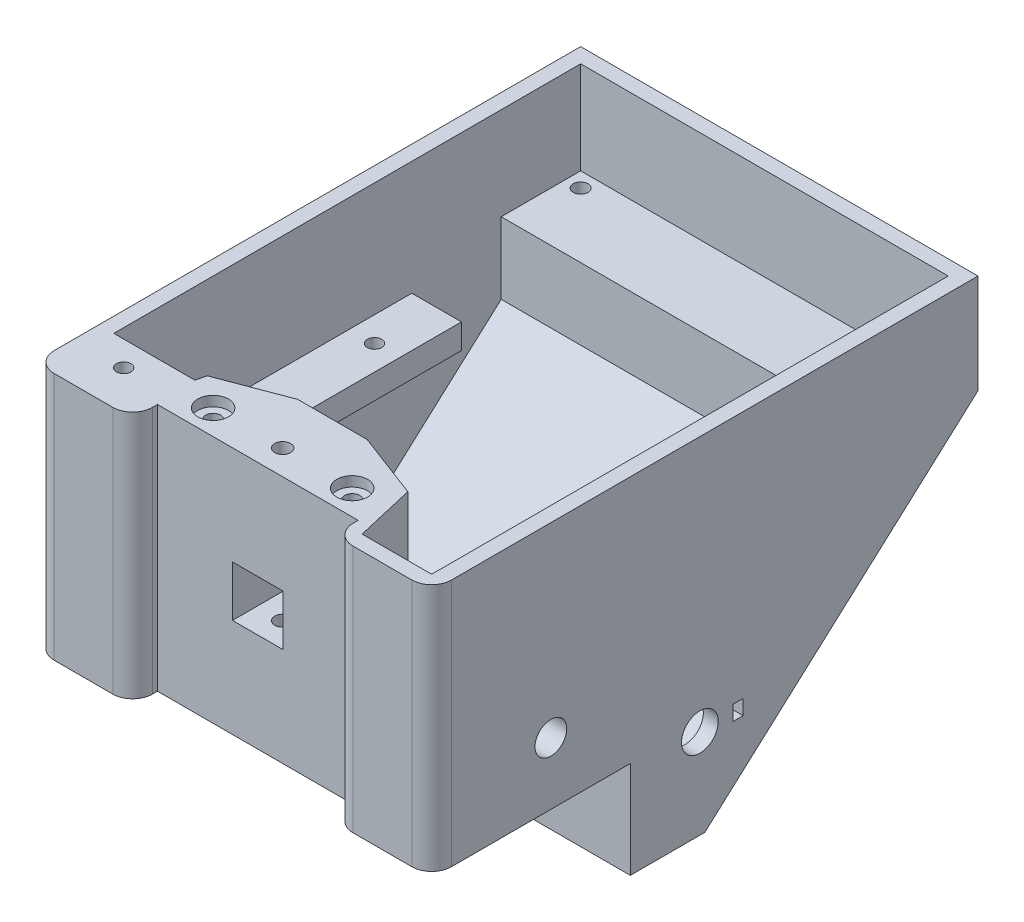
SolidWorks part; units mm, degrees
ref_plane "Спереди" through (0, 0, 0) normal (0, 0, 1) x (1, 0, 0)
ref_plane "Сверху" through (0, 0, 0) normal (0, 1, 0) x (1, 0, 0)
ref_plane "Справа" through (0, 0, 0) normal (1, 0, 0) x (0, 0, -1)
sketch "Sketch2" plane through (0, 0, 0) normal (1, 0, 0) x (0, 0, -1)
  line L0 (-27.3205, 20.9982) -> (-27.3205, -29.0018)
  line L1 (-27.3205, -29.0018) -> (12.6795, -29.0018)
  line L2 (12.6795, -29.0018) -> (12.6795, -48.5114)
  line L3 (12.6795, -48.5114) -> (27.6795, -48.5114)
  line L4 (82.6795, 20.9982) -> (82.6795, 0.9982)
  line L5 (82.6795, 20.9982) -> (-27.3205, 20.9982)
  line L6 (82.6795, 0.9982) -> (27.6795, -48.5114)
  dimension "D1" = 110
  dimension "D2" = 50
  dimension "D3" = 40
  dimension "D4" = 15
  dimension "D5" = 20
extrude "Boss-Extrude1" add sketch "Sketch2" along normal blind 80
shell "Shell1" thickness 3 removed face at (40, 20.9982, -27.6795)
sketch "Sketch3" plane through (0, 0, 24.3205) normal (0, 0, -1) x (-1, 0, 0)
  line L0 (-40, 20.9982) -> (-40, -26.0018) construction
  line L3 (-77, 20.9982) -> (-3, 20.9982) construction
  line L4 (-77, -26.0018) -> (-3, -26.0018) construction
  line L6 (-17, 20.9982) -> (-63, 20.9982)
  line L7 (-17, 20.9982) -> (-17, -26.0018)
  line L8 (-17, -26.0018) -> (-63, -26.0018)
  line L9 (-63, 20.9982) -> (-63, -26.0018)
  line L10 (-17, 20.9982) -> (-63, -26.0018) construction
  line L11 (-17, -26.0018) -> (-63, 20.9982) construction
  point P6 (-40, -2.5018)
  dimension "D1" = 46
extrude "Boss-Extrude2" add sketch "Sketch3" along normal blind 17
sketch "Sketch4" plane through (0, 0, 27.3205) normal (0, 0, 1) x (1, 0, 0)
  line L0 (0, 20.9982) -> (80, -29.0018) construction
  line L2 (45.1, -9.1018) -> (34.9, -9.1018)
  line L3 (45.1, -9.1018) -> (45.1, 1.0982)
  line L4 (45.1, 1.0982) -> (34.9, 1.0982)
  line L5 (34.9, -9.1018) -> (34.9, 1.0982)
  line L6 (45.1, -9.1018) -> (34.9, 1.0982) construction
  line L7 (45.1, 1.0982) -> (34.9, -9.1018) construction
  point P4 (40, -4.0018)
  dimension "D1" = 10.2
extrude "Cut-Extrude1" cut sketch "Sketch4" against normal up to surface (20 mm away) up to face at (40, -2.5018, 7.3205)
sketch "Sketch6" plane through (0, -29.0018, 0) normal (0, -1, 0) x (1, 0, 0)
  line L0 (40, 27.3205) -> (40, -12.6795) construction
  line L1 (47.5, -5.4795) -> (32.5, -5.4795)
  line L2 (47.5, -5.4795) -> (47.5, 7.3205)
  line L3 (47.5, 7.3205) -> (32.5, 7.3205)
  line L4 (32.5, -5.4795) -> (32.5, 7.3205)
  line L5 (47.5, -5.4795) -> (32.5, 7.3205) construction
  line L6 (47.5, 7.3205) -> (32.5, -5.4795) construction
  line L7 (80, -12.6795) -> (0, -12.6795) construction
  line L9 (80, 27.3205) -> (0, 27.3205) construction
  point P0 (40, 0.9205)
  dimension "D1" = 15
  dimension "D2" = 12.8
  dimension "D4" = 20
extrude "Cut-Extrude2" cut sketch "Sketch6" against normal up to surface (3 mm away) up to face at (40, -26.0018, 10.0705)
sketch "Sketch7" plane through (0, 0, 27.3205) normal (0, 0, 1) x (1, 0, 0)
  line L0 (40, 20.9982) -> (40, -29.0018) construction
  line L1 (80, 20.9982) -> (0, 20.9982) construction
  line L2 (80, -29.0018) -> (0, -29.0018) construction
  line L4 (60.2, -29.0018) -> (19.8, -29.0018)
  line L5 (60.2, -29.0018) -> (60.2, 20.9982)
  line L6 (60.2, 20.9982) -> (19.8, 20.9982)
  line L7 (19.8, -29.0018) -> (19.8, 20.9982)
  line L8 (60.2, -29.0018) -> (19.8, 20.9982) construction
  line L9 (60.2, 20.9982) -> (19.8, -29.0018) construction
  point P6 (40, -4.0018)
  dimension "D1" = 40.4
extrude "Cut-Extrude3" cut sketch "Sketch7" against normal blind 5
fillet "Fillet1" radius 4 4 edges at (19.8, -4.0018, 27.3205) (60.2, -4.0018, 27.3205) (80, -4.0018, 27.3205) (0, -4.0018, 27.3205)
sketch "Sketch12" plane through (0, 20.9982, 0) normal (0, 1, 0) x (1, 0, 0)
  line L0 (19.8, -22.3205) -> (19.8, -12.3205) construction
  line L1 (19.8, -12.3205) -> (60.2, -12.3205) construction
  line L2 (60.2, -12.3205) -> (60.2, -22.3205) construction
  line L3 (33, -7.3205) -> (19.8, -12.3205)
  line L4 (17, -7.3205) -> (63, -7.3205) construction
  line L5 (19.8, -12.3205) -> (17, -24.3205)
  line L6 (17, -24.3205) -> (17, -7.3205)
  line L7 (17, -7.3205) -> (33, -7.3205)
  line L8 (47, -7.3205) -> (63, -7.3205)
  line L9 (63, -7.3205) -> (63, -24.3205)
  line L10 (63, -24.3205) -> (60.2, -12.3205)
  line L11 (60.2, -12.3205) -> (47, -7.3205)
  dimension "D1" = 10
  dimension "D2" = 16
extrude "Cut-Extrude7" cut sketch "Sketch12" against normal up to surface (47 mm away) up to face at (40, -26.0018, 7.0205)
sketch "Sketch13" plane through (0, 20.9982, 0) normal (0, 1, 0) x (1, 0, 0)
  line L0 (19.8, -22.3205) -> (19.8, -12.3205) construction
  line L1 (19.8, -12.3205) -> (60.2, -12.3205) construction
  line L2 (60.2, -12.3205) -> (60.2, -22.3205) construction
  line L3 (60.2, -17.3205) -> (19.8, -17.3205) construction
  circle A0 centre (26, -17.3205) radius 1.5
  circle A1 centre (54, -17.3205) radius 1.5
  point P14 (40, -17.3205)
  dimension "D1" = 3
  dimension "D2" = 28
  dimension "D3" = 14
  dimension "D4" = 6.2
extrude "Cut-Extrude8" cut sketch "Sketch13" against normal blind 25
sketch "Sketch14" plane through (0, 20.9982, 0) normal (0, 1, 0) x (1, 0, 0)
  circle A0 centre (26, -17.3205) radius 3.1
  circle A1 centre (54, -17.3205) radius 3.1
  dimension "D1" = 6.2
extrude "Cut-Extrude9" cut sketch "Sketch14" against normal blind 2
sketch "Sketch17" plane through (77, 0, 0) normal (-1, 0, 0) x (0, 0, 1)
  line L0 (-45.6795, -2.0018) -> (-0.6795, -2.0018)
  line L1 (-0.6795, -2.0018) -> (-0.6795, -7.0018)
  line L2 (-0.6795, -7.0018) -> (-45.6795, -7.0018)
  line L3 (-45.6795, -7.0018) -> (-45.6795, -2.0018)
  line L4 (-79.6795, 20.9982) -> (24.3205, 20.9982) construction
  line L5 (-79.6795, 2.3342) -> (-79.6795, 20.9982) construction
  dimension "D1" = 45
  dimension "D2" = 5
  dimension "D3" = 23
  dimension "D4" = 34
extrude "Boss-Extrude5" add sketch "Sketch17" along normal up to surface (74 mm away) up to face at (3, -14.0994, -24.0865)
sketch "Sketch18" plane through (0, -2.0018, 0) normal (0, 1, 0) x (1, 0, 0)
  line L0 (40, 0.6795) -> (40, 45.6795) construction
  line L1 (3, 0.6795) -> (77, 0.6795) construction
  line L2 (3, 45.6795) -> (77, 45.6795) construction
  line L3 (77, 0.6795) -> (77, 45.6795) construction
  line L4 (13, 0.6795) -> (67, 0.6795)
  line L5 (13, 0.6795) -> (13, 45.6795)
  line L6 (13, 45.6795) -> (67, 45.6795)
  line L7 (67, 0.6795) -> (67, 45.6795)
  line L8 (13, 0.6795) -> (67, 45.6795) construction
  line L9 (13, 45.6795) -> (67, 0.6795) construction
  point P6 (40, 23.1795)
  dimension "D1" = 10
extrude "Cut-Extrude10" cut sketch "Sketch18" against normal up to next
sketch "Sketch19" plane through (0, -2.0018, 0) normal (0, 1, 0) x (1, 0, 0)
  line L0 (72, 45.6795) -> (72, 0.6795) construction
  line L1 (67, 45.6795) -> (77, 45.6795) construction
  line L2 (67, 0.6795) -> (77, 0.6795) construction
  line L3 (8, 45.6795) -> (8, 0.6795) construction
  line L4 (3, 45.6795) -> (13, 45.6795) construction
  line L5 (3, 0.6795) -> (13, 0.6795) construction
  circle A0 centre (72, 37.1795) radius 1.45
  circle A1 centre (72, 6.1795) radius 1.45
  circle A2 centre (8, 33.1795) radius 1.45
  circle A3 centre (8, 6.1795) radius 1.45
  point P20 (72, 23.1795)
  point P21 (8, 23.1795)
  dimension "D1" = 2.9
  dimension "D2" = 14
  dimension "D3" = 17
  dimension "D4" = 17
  dimension "D5" = 10
extrude "Cut-Extrude11" cut sketch "Sketch19" against normal up to next
sketch "Sketch21" plane through (0, -26.0018, 0) normal (0, 1, 0) x (1, 0, 0)
  line L0 (3, -24.3205) -> (3, -14.3205)
  line L1 (3, -24.3205) -> (3, 15.6795) construction
  line L2 (3, -14.3205) -> (19.3333, -14.3205)
  line L3 (19.8, -12.3205) -> (17, -24.3205) construction
  line L4 (19.3333, -14.3205) -> (17, -24.3205)
  line L6 (3, -24.3205) -> (17, -24.3205)
  dimension "D1" = 10
extrude "Boss-Extrude6" add sketch "Sketch21" along normal up to surface (47 mm away) up to face at (54, 20.9982, 20.4205)
sketch "Sketch22" plane through (0, 20.9982, 0) normal (0, 1, 0) x (1, 0, 0)
  line L0 (0, 82.6795) -> (0, -23.3205) construction
  line L1 (15.8, -27.3205) -> (4, -27.3205) construction
  circle A0 centre (10, -19.3205) radius 1.45
  dimension "D1" = 2.9
  dimension "D2" = 10
  dimension "D3" = 8
extrude "Cut-Extrude12" cut sketch "Sketch22" against normal through all
sketch "Sketch24" plane through (80, 0, 0) normal (1, 0, 0) x (0, 0, -1)
  line L0 (12.6795, -48.5114) -> (27.6795, -48.5114) construction
  line L1 (12.6795, -29.0018) -> (12.6795, -48.5114) construction
  line L2 (18.1795, -30.5114) -> (18.1795, -19.0114) construction
  line L3 (18.1795, -19.0114) -> (35.1795, -19.0114) construction
  line L4 (35.1795, -19.0114) -> (35.1795, -30.5114) construction
  line L5 (26.6795, -19.0114) -> (26.6795, -39.0114) construction
  line L6 (30.3795, -30.5114) -> (34.3795, -30.5114) construction
  line L8 (33.3795, -32.0114) -> (35.3795, -32.0114)
  line L9 (33.3795, -32.0114) -> (33.3795, -29.0114)
  line L10 (33.3795, -29.0114) -> (35.3795, -29.0114)
  line L11 (35.3795, -32.0114) -> (35.3795, -29.0114)
  line L12 (33.3795, -32.0114) -> (35.3795, -29.0114) construction
  line L13 (33.3795, -29.0114) -> (35.3795, -32.0114) construction
  circle A0 centre (26.6795, -30.5114) radius 3.7
  circle A1 centre (26.6795, -30.5114) radius 8.5 construction
  dimension "D1" = 7.4
  dimension "D2" = 17
  dimension "D3" = 18
  dimension "D4" = 14
  dimension "D5" = 20
  dimension "D6" = 4
  dimension "D7" = 2
  dimension "D8" = 3
extrude "Cut-Extrude13" cut sketch "Sketch24" against normal up to next
sketch "Sketch26" plane through (3, 0, 0) normal (1, 0, 0) x (0, 0, -1)
  line L0 (79.6795, 2.3342) -> (63.6795, 2.3342)
  line L1 (63.6795, 2.3342) -> (63.6795, -12.0686)
  line L2 (26.5281, -45.5114) -> (79.6795, 2.3342) construction
  line L3 (63.6795, -12.0686) -> (79.6795, 2.3342)
  dimension "D1" = 16
extrude "Boss-Extrude7" add sketch "Sketch26" along normal up to surface (74 mm away) up to face at (77, -30.5114, -34.3795)
sketch "Sketch27" plane through (0, 2.3342, 0) normal (0, 1, 0) x (1, 0, 0)
  line L0 (3, 76.6795) -> (77, 76.6795) construction
  line L1 (3, 79.6795) -> (3, 63.6795) construction
  line L2 (77, 79.6795) -> (77, 63.6795) construction
  line L3 (80, 82.6795) -> (0, 82.6795) construction
  circle A0 centre (6, 76.6795) radius 1.5
  circle A1 centre (74, 76.6795) radius 1.5
  point P10 (40, 76.6795)
  dimension "D1" = 3
  dimension "D2" = 68
  dimension "D3" = 34
  dimension "D4" = 6
extrude "Cut-Extrude14" cut sketch "Sketch27" against normal blind 10
sketch "Sketch28" plane through (0, 2.3342, 0) normal (0, 1, 0) x (1, 0, 0)
  line L1 (74, 79.9295) -> (71.1854, 78.3045)
  line L2 (71.1854, 78.3045) -> (71.1854, 75.0545)
  line L3 (71.1854, 75.0545) -> (74, 73.4295)
  line L4 (74, 73.4295) -> (76.8146, 75.0545)
  line L5 (76.8146, 75.0545) -> (76.8146, 78.3045)
  line L6 (76.8146, 78.3045) -> (74, 79.9295)
  line L7 (6, 73.4295) -> (8.8146, 75.0545)
  line L8 (8.8146, 75.0545) -> (8.8146, 78.3045)
  line L9 (8.8146, 78.3045) -> (6, 79.9295)
  line L10 (6, 79.9295) -> (3.1854, 78.3045)
  line L11 (3.1854, 78.3045) -> (3.1854, 75.0545)
  line L12 (3.1854, 75.0545) -> (6, 73.4295)
  circle A0 centre (74, 76.6795) radius 3.25 construction
  circle A1 centre (6, 76.6795) radius 3.25 construction
  dimension "D1" = 6.5
extrude "Cut-Extrude15" cut sketch "Sketch28" against normal blind 32 from offset 3 offset against normal yes
sketch "Sketch29" plane through (0, -29.0018, 0) normal (0, -1, 0) x (1, 0, 0)
  line L0 (0, 23.3205) -> (0, -12.6795) construction
  line L1 (7.1854, 17.6955) -> (10, 16.0705)
  line L2 (10, 16.0705) -> (12.8146, 17.6955)
  line L3 (12.8146, 17.6955) -> (12.8146, 20.9455)
  line L4 (12.8146, 20.9455) -> (10, 22.5705)
  line L5 (10, 22.5705) -> (7.1854, 20.9455)
  line L6 (7.1854, 20.9455) -> (7.1854, 17.6955)
  circle A0 centre (10, 19.3205) radius 3.25 construction
  dimension "D1" = 6.5
extrude "Cut-Extrude16" cut sketch "Sketch29" against normal blind 30
sketch "Sketch30" plane through (0, -26.0018, 0) normal (0, 1, 0) x (1, 0, 0)
  line L0 (77, -24.3205) -> (63, -24.3205)
  line L1 (63, -24.3205) -> (60.2, -12.3205)
  line L2 (63, -24.3205) -> (60.2, -12.3205) construction
  line L3 (60.2, -12.3205) -> (77, -12.3205)
  line L4 (77, -24.3205) -> (77, 15.6795) construction
  line L5 (77, -12.3205) -> (77, -24.3205)
  dimension "D1" = 12
extrude "Boss-Extrude8" add sketch "Sketch30" along normal blind 20
sketch "Sketch31" plane through (0, -6.0018, 0) normal (0, 1, 0) x (1, 0, 0)
  line L0 (76, -27.3205) -> (64.2, -27.3205) construction
  line L1 (80, -23.3205) -> (80, 12.6795) construction
  circle A0 centre (72, -21.3205) radius 1.5
  dimension "D3" = 3
  dimension "D1" = 6
  dimension "D2" = 8
extrude "Cut-Extrude17" cut sketch "Sketch31" against normal through all
sketch "Sketch32" plane through (0, -29.0018, 0) normal (0, -1, 0) x (1, 0, 0)
  line L1 (72, 24.5705) -> (69.1854, 22.9455)
  line L2 (69.1854, 22.9455) -> (69.1854, 19.6955)
  line L3 (69.1854, 19.6955) -> (72, 18.0705)
  line L4 (72, 18.0705) -> (74.8146, 19.6955)
  line L5 (74.8146, 19.6955) -> (74.8146, 22.9455)
  line L6 (74.8146, 22.9455) -> (72, 24.5705)
  circle A0 centre (72, 21.3205) radius 3.25 construction
  dimension "D1" = 6.5
extrude "Cut-Extrude18" cut sketch "Sketch32" against normal blind 15
sketch "Sketch33" plane through (0, -2.0018, 0) normal (0, 1, 0) x (1, 0, 0)
  line L0 (67, 40.6795) -> (77, 40.6795)
  line L1 (67, 0.6795) -> (67, 45.6795) construction
  line L2 (77, 0.6795) -> (77, 45.6795) construction
  line L3 (77, 40.6795) -> (77, 45.6795)
  line L4 (77, 45.6795) -> (67, 45.6795)
  line L5 (67, 45.6795) -> (67, 40.6795)
  dimension "D1" = 5
extrude "Cut-Extrude19" cut sketch "Sketch33" against normal up to next
sketch "Sketch34" plane through (0, 20.9982, 0) normal (0, 1, 0) x (1, 0, 0)
  line L0 (54, -17.3205) -> (26, -17.3205) construction
  circle A0 centre (40, -17.3205) radius 1.6
  dimension "D1" = 3.2
extrude "Cut-Extrude20" cut sketch "Sketch34" against normal through all
sketch "Sketch36" plane through (0, -29.0018, 0) normal (0, -1, 0) x (1, 0, 0)
  line L1 (38.375, 20.1351) -> (36.75, 17.3205)
  line L2 (36.75, 17.3205) -> (38.375, 14.5059)
  line L3 (38.375, 14.5059) -> (41.625, 14.5059)
  line L4 (41.625, 14.5059) -> (43.25, 17.3205)
  line L5 (43.25, 17.3205) -> (41.625, 20.1351)
  line L6 (41.625, 20.1351) -> (38.375, 20.1351)
  circle A0 centre (40, 17.3205) radius 3.25 construction
  dimension "D1" = 6.5
extrude "Cut-Extrude22" cut sketch "Sketch36" against normal blind 14
sketch "Sketch37" plane through (80, 0, 0) normal (1, 0, 0) x (0, 0, -1)
  line L0 (-23.3205, -16.5114) -> (63.2281, -16.5114) construction
  line L1 (-23.3205, 20.9982) -> (-23.3205, -29.0018) construction
  line L2 (27.6795, -48.5114) -> (82.6795, 0.9982) construction
  line L3 (30.3795, -30.5114) -> (22.9795, -30.5114) construction
  circle A0 centre (-3.3205, -16.5114) radius 3.2
  circle A1 centre (26.6795, -30.5114) radius 3.7 construction
  point P14 (26.6795, -30.5114)
  dimension "D1" = 6.4
  dimension "D2" = 14
  dimension "D3" = 20
extrude "Cut-Extrude23" cut sketch "Sketch37" against normal up to next
sketch "Sketch38" plane through (77, 0, 0) normal (-1, 0, 0) x (0, 0, 1)
  line L0 (12.3205, -26.0018) -> (-15.6795, -26.0018) construction
  line L1 (8.3205, -7.021) -> (-1.6795, -7.021)
  line L2 (8.3205, -7.021) -> (8.3205, -26.0018)
  line L3 (8.3205, -26.0018) -> (-1.6795, -26.0018)
  line L4 (-1.6795, -7.021) -> (-1.6795, -26.0018)
  line L5 (8.3205, -7.021) -> (-1.6795, -26.0018) construction
  line L6 (8.3205, -26.0018) -> (-1.6795, -7.021) construction
  circle A0 centre (3.3205, -16.5114) radius 3.2
  point P0 (3.3205, -16.5114)
  dimension "D1" = 10
extrude "Boss-Extrude9" add sketch "Sketch38" along normal blind 3
